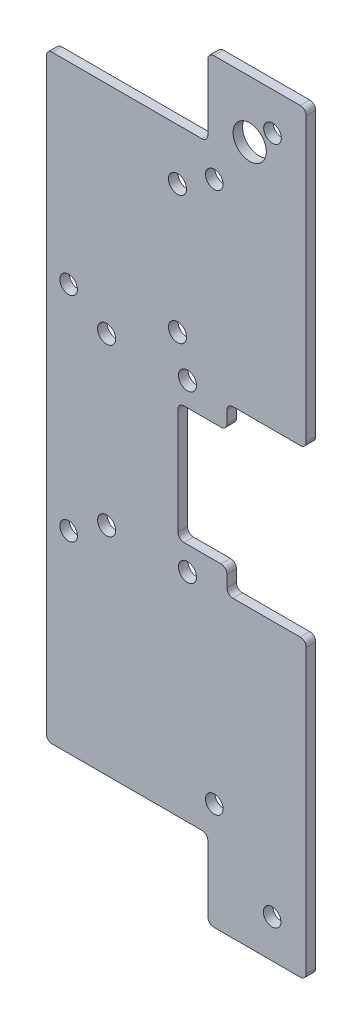
SolidWorks part; units mm, degrees
material "Thornel Mat VMA"
ref_plane "Front Plane" through (0, 0, 0) normal (0, 0, 1) x (1, 0, 0)
ref_plane "Top Plane" through (0, 0, 0) normal (0, 1, 0) x (1, 0, 0)
ref_plane "Right Plane" through (0, 0, 0) normal (1, 0, 0) x (0, 0, -1)
sketch "Sketch1" plane through (0, 0, 0) normal (0, 0, 1) x (1, 0, 0)
  line L0 (-2.9301, -104.5098) -> (-3.3149, -104.5098)
  line L1 (-3.3149, -72.8868) -> (-2.9301, -72.8868)
  line L78 (45.3299, -66.5368) -> (45.3299, -72.8868)
  line L79 (45.3299, -104.5098) -> (45.3299, -110.8598)
  line L80 (66.5174, -66.5368) -> (105.3971, 12.1397)
  line L81 (105.3971, 12.1397) -> (38.7094, 12.1397)
  line L88 (38.7094, 12.1397) -> (38.7094, -8.6883)
  line L89 (-2.9301, -8.6883) -> (38.7094, -8.6883)
  line L90 (-3.3149, -53.8368) -> (-2.9301, -53.8368)
  line L91 (-2.9301, -53.8368) -> (-2.9301, -8.6883)
  line L92 (-3.3149, -66.5368) -> (-3.3149, -53.8368)
  line L93 (-3.3149, -72.8868) -> (-3.3149, -66.5368)
  line L94 (-2.9301, -104.5098) -> (-2.9301, -72.8868)
  line L95 (-3.3149, -110.8598) -> (-3.3149, -104.5098)
  line L96 (66.5174, -110.8598) -> (105.3971, -189.5363)
  line L97 (105.3971, -189.5363) -> (38.7094, -189.5363)
  line L98 (38.7094, -189.5363) -> (38.7094, -168.7083)
  line L99 (-2.9301, -168.7083) -> (38.7094, -168.7083)
  line L106 (-3.3149, -110.8598) -> (-3.3149, -123.5598)
  line L107 (-3.3149, -123.5598) -> (-2.9301, -123.5598)
  line L108 (66.5174, -110.8598) -> (45.3299, -110.8598)
  line L109 (45.3299, -66.5368) -> (66.5174, -66.5368)
  line L110 (45.3299, -104.5098) -> (45.3299, -72.8868)
  line L111 (-2.9301, -123.5598) -> (-2.9301, -168.7083)
  circle A0 centre (90.6739, 2.6147) radius 2.3495
  circle A1 centre (41.9566, -16.4353) radius 2.3495
  circle A2 centre (3.0351, -60.1868) radius 2.3495
  circle A3 centre (3.0351, -117.2098) radius 2.3495
  circle A4 centre (41.9566, -160.9613) radius 2.3495
  circle A5 centre (90.6739, -180.0113) radius 2.3495
  circle A6 centre (51.4094, -3.1003) radius 4.445
  point P2 (90.6739, 2.6147)
  point P4 (41.9566, -16.4353)
  point P6 (3.0351, -60.1868)
  point P8 (3.0351, -117.2098)
  point P10 (41.9566, -160.9613)
  point P11 (90.6739, -180.0113)
  dimension "D2" = 4.699
  dimension "D5" = 8.89
  dimension "D1" = 66.6876
  dimension "D3" = 12.7
  dimension "D4" = 15.24
  dimension "D6" = 48.26
extrude "Boss-Extrude1" add sketch "Sketch1" along normal blind 2.54
sketch "Sketch2" plane through (0, 0, 2.54) normal (0, 0, 1) x (1, 0, 0)
  line L0 (-3.3149, -53.8368) -> (-3.3149, -72.8868) construction
  line L1 (45.3299, -66.5368) -> (66.5174, -66.5368) construction
  line L2 (45.3299, -88.6983) -> (-2.9301, -88.6983) construction
  line L3 (45.3299, -110.8598) -> (45.3299, -66.5368) construction
  line L4 (-2.9301, -72.8868) -> (-2.9301, -104.5098) construction
  circle A0 centre (13.1951, -66.5368) radius 2.413
  circle A2 centre (34.7851, -66.5368) radius 2.413
  circle A4 centre (34.7851, -110.8598) radius 2.413
  circle A6 centre (13.1951, -110.8598) radius 2.413
  dimension "D1" = 4.826
  dimension "D2" = 21.59
  dimension "D3" = 4.826
  dimension "D5" = 16.51
  dimension "D7" = 0
extrude "Cut-Extrude1" cut sketch "Sketch2" against normal through all
sketch "Sketch3" plane through (0, 0, 2.54) normal (0, 0, 1) x (1, 0, 0)
  line L0 (45.3299, -110.8598) -> (45.3299, -66.5368) construction
  line L1 (45.3299, -72.8868) -> (32.2451, -72.8868)
  line L2 (45.3299, -72.8868) -> (45.3299, -104.5098)
  line L3 (45.3299, -104.5098) -> (32.2451, -104.5098)
  line L4 (32.2451, -72.8868) -> (32.2451, -104.5098)
  line L5 (45.3299, -66.5368) -> (66.5174, -66.5368) construction
  line L6 (66.5174, -110.8598) -> (45.3299, -110.8598) construction
  circle A1 centre (13.1951, -66.5368) radius 2.413 construction
  dimension "D3" = 19.05
  dimension "D1" = 6.35
  dimension "D2" = 6.35
extrude "Cut-Extrude2" cut sketch "Sketch3" against normal through all
sketch "Sketch4" plane through (0, 0, 2.54) normal (0, 0, 1) x (1, 0, 0)
  line L0 (-2.9301, -168.7083) -> (38.7094, -168.7083) construction
  line L1 (27.4577, 15.7469) -> (40.2334, 15.7469)
  line L2 (27.4577, 15.7469) -> (27.4577, -8.6883)
  line L3 (27.4577, -8.6883) -> (40.2334, -8.6883)
  line L4 (40.2334, 15.7469) -> (40.2334, -8.6883)
  line L5 (0, -197.042) -> (40.2334, -197.042)
  line L6 (0, -197.042) -> (0, -168.7083)
  line L7 (0, -168.7083) -> (40.2334, -168.7083)
  line L8 (40.2334, -197.042) -> (40.2334, -168.7083)
  line L9 (38.7094, -168.7083) -> (38.7094, -189.5363) construction
  line L10 (38.7094, -8.6883) -> (-2.9301, -8.6883) construction
  dimension "D1" = 1.524
extrude "Cut-Extrude3" cut sketch "Sketch4" against normal through all
sketch "Sketch5" plane through (0, 0, 0) normal (0, 0, -1) x (-1, 0, 0)
  line L0 (2.9301, -8.6883) -> (2.9301, -53.8368) construction
  line L1 (-40.2334, -8.6883) -> (2.9301, -8.6883) construction
  circle A0 centre (-32.1219, -22.4043) radius 2.413
  circle A1 centre (-32.1219, -56.6943) radius 2.413
  dimension "D4" = 4.826
  dimension "D1" = 35.052
  dimension "D2" = 13.716
  dimension "D3" = 34.29
extrude "Cut-Extrude4" cut sketch "Sketch5" against normal through all
sketch "Sketch7" plane through (0, 0, 2.54) normal (0, 0, 1) x (1, 0, 0)
  line L0 (66.5174, -66.5368) -> (66.5174, 21.5221)
  line L1 (66.5174, 21.5221) -> (127.8208, 21.5221)
  line L2 (66.5174, -110.8598) -> (66.5174, -200.2563)
  line L3 (66.5174, -200.2563) -> (115.7822, -200.2563)
  line L4 (115.7822, -200.2563) -> (127.8208, 21.5221)
  line L5 (66.5174, -66.5368) -> (66.5174, -110.8598)
extrude "Cut-Extrude5" cut sketch "Sketch7" against normal through all both and the other way through all
extrude "Cut-Extrude6" cut sketch "Sketch8" against normal through all
sketch "Sketch8" plane through (13.5516, -164.5272, 0) normal (0, 0, -1) x (0.9999, -0.0134, 0)
  circle A0 centre (41.7212, -167.1203) radius 2.3495
  circle A1 centre (44.0495, 14.2195) radius 2.3495
fillet "Fillet1" radius 1.5875 16 edges at (-2.9301, -168.7083, 1.27) (40.2334, -168.7083, 1.27) (40.2334, -189.5363, 1.27) (66.5174, -189.5363, 1.27) (66.5174, -110.8598, 1.27) (45.3299, -110.8598, 1.27) (45.3299, -104.5098, 1.27) (32.2451, -104.5098, 1.27) (32.2451, -72.8868, 1.27) (45.3299, -72.8868, 1.27) (45.3299, -66.5368, 1.27) (66.5174, -66.5368, 1.27) (66.5174, 12.1397, 1.27) (40.2334, 12.1397, 1.27) (40.2334, -8.6883, 1.27) (-2.9301, -8.6883, 1.27)
sketch "Sketch9" plane through (0, -123.5598, 0) normal (0, -1, 0) x (1, 0, 0)
  line L1 (-3.3149, 2.54) -> (-2.9301, 2.54)
  line L2 (-3.3149, 2.54) -> (-3.3149, 0)
  line L3 (-3.3149, 0) -> (-2.9301, 0)
  line L4 (-2.9301, 2.54) -> (-2.9301, 0)
extrude "Cut-Extrude7" cut sketch "Sketch9" against normal through all
